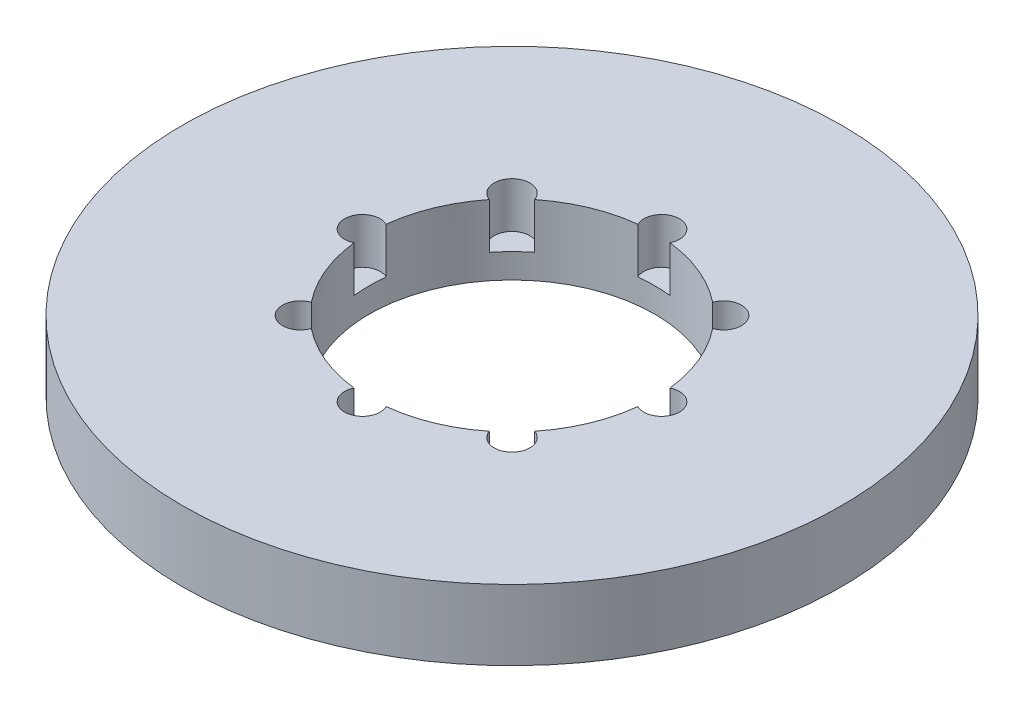
SolidWorks part; units mm, degrees
ref_plane "Front Plane" through (0, 0, 0) normal (0, 0, 1) x (1, 0, 0)
ref_plane "Top Plane" through (0, 0, 0) normal (0, 1, 0) x (1, 0, 0)
ref_plane "Right Plane" through (0, 0, 0) normal (1, 0, 0) x (0, 0, -1)
sketch "Sketch1" plane through (0, 0, 0) normal (0, 1, 0) x (1, 0, 0)
  circle A0 centre (0, 0) radius 75
  dimension "FLANGE_OD" = 150
extrude "Boss-Extrude1" add sketch "Sketch1" along normal blind 16
sketch "Sketch2" plane through (0, 0, 0) normal (0, 1, 0) x (1, 0, 0)
  circle A0 centre (0, 0) radius 32.5
  dimension "BORE_D" = 65
extrude "Cut-Extrude1" cut sketch "Sketch2" along normal through all
sketch "Sketch3" plane through (0, 16, 0) normal (0, 1, 0) x (1, 0, 0)
  circle A0 centre (0, 0) radius 34.0539 construction
  circle A1 centre (-34.0539, 0) radius 4.0593
  dimension "BOLT_D" = 8.1186
  dimension "BOLT_PCD" = 68.1078
extrude "Cut-Extrude2" cut sketch "Sketch3" against normal blind 10.4016
pattern_circular "CirPattern1" count 8 over 360 about axis through (0, 0, 0) along (0, 1, 0) of "Cut-Extrude2"
